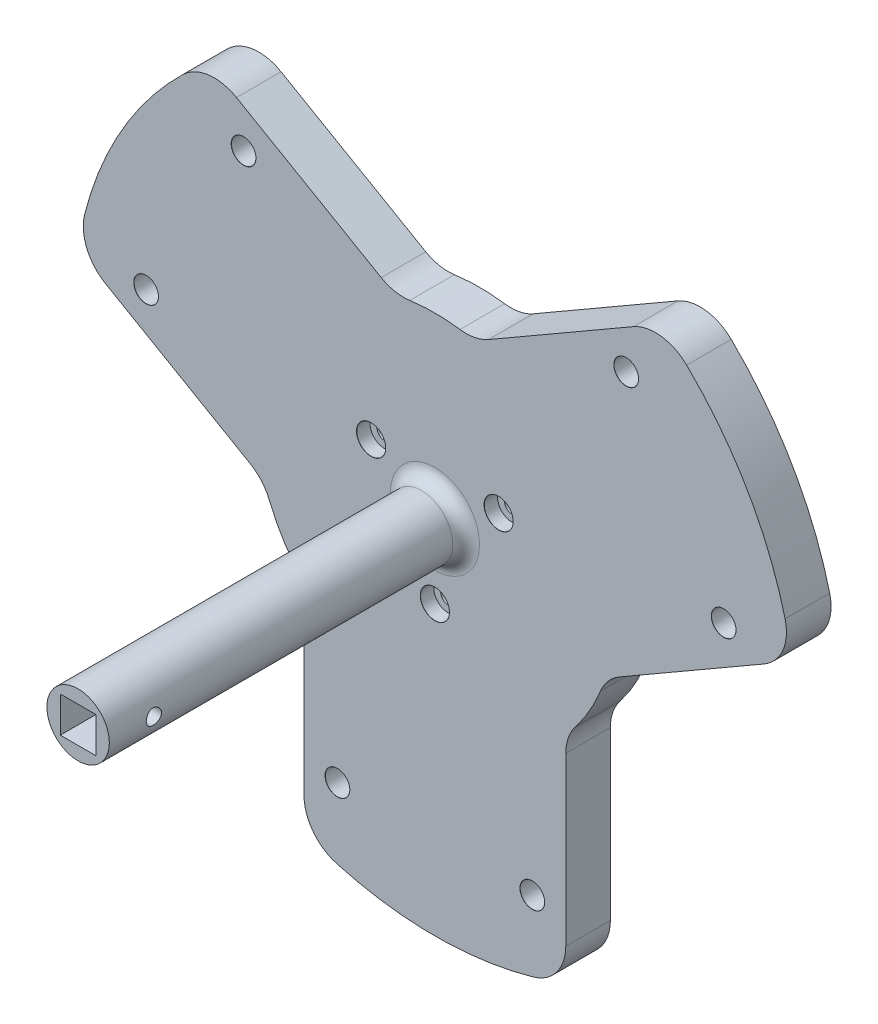
SolidWorks part; units mm, degrees
ref_plane "Front Plane" through (0, 0, 0) normal (0, 0, 1) x (1, 0, 0)
ref_plane "Top Plane" through (0, 0, 0) normal (0, 1, 0) x (1, 0, 0)
ref_plane "Right Plane" through (0, 0, 0) normal (1, 0, 0) x (0, 0, -1)
sketch "Sketch1" plane through (0, 0, 0) normal (0, 0, 1) x (1, 0, 0)
  circle A0 centre (0, 0) radius 81
  dimension "D1" = 162
extrude "Boss-Extrude1" add sketch "Sketch1" along normal blind 10
ref_axis "Axis2" through (0, 0, 38.9853) along (0, 0, -1)
sketch "Sketch2" plane through (0, 0, 10) normal (0, 0, 1) x (1, 0, 0)
  line L0 (0, 0) -> (0, -16.51) construction
  line L1 (-14.2981, 8.255) -> (0, 0) construction
  line L2 (0, 0) -> (14.2981, 8.255) construction
  circle A0 centre (0, 0) radius 16.51 construction
  point P7 (-14.2981, 8.255)
  point P8 (14.2981, 8.255)
  point P9 (0, -16.51)
  dimension "D1" = 16.51
  dimension "D2" = 120
  dimension "D3" = 120
sketch "Sketch5" plane through (0, 0, 10) normal (0, 0, 1) x (1, 0, 0)
  point P0 (-14.2981, 8.255)
  point P3 (14.2981, 8.255)
  point P6 (0, -16.51)
hole_wizard "CBORE for M3 SHCS1" positions "Sketch5" profile "Sketch4" counterbore size "M3" standard "ANSI Metric" end condition up to next
sketch "Sketch4" plane through (-14.2981, 8.255, 10) normal (1, 0, 0) x (0, -1, 0)
  line L0 (0, 0) -> (0, 10)
  line L1 (0, 10) -> (1.7, 10)
  line L3 (1.7, 10) -> (1.7, 3)
  line L4 (3.25, 3) -> (1.7, 3)
  line L5 (3.25, 3) -> (3.25, 0.025)
  line L6 (3.25, 0.025) -> (3.275, 0)
  line L7 (3.275, 0) -> (0, 0)
  line L8 (-3.25, 0.025) -> (-3.275, 0) construction
  line L11 (0, -6.35) -> (0, 107.95) construction
  dimension "Thru Hole Dia." = 3.4
  dimension "Thru Hole Depth" = 10
  dimension "C'Bore Dia." = 6.5
  dimension "C'Bore Depth" = 3
  dimension "Near C'Sink Dia." = 6.55
  dimension "Near C'Sink Angle" = 90
sketch "Sketch6" plane through (0, 0, 10) normal (0, 0, 1) x (1, 0, 0)
  circle A0 centre (0, 0) radius 7
  dimension "D1" = 14
extrude "Boss-Extrude2" add sketch "Sketch6" along normal blind 80
sketch "Sketch20" plane through (0, 0, 90) normal (0, 0, 1) x (1, 0, 0)
  line L1 (-4, 4) -> (4, 4)
  line L2 (-4, 4) -> (-4, -4)
  line L3 (-4, -4) -> (4, -4)
  line L4 (4, 4) -> (4, -4)
  line L5 (-4, 4) -> (4, -4) construction
  line L6 (-4, -4) -> (4, 4) construction
  point P0 (0, 0)
  dimension "D1" = 8
extrude "Cut-Extrude1" cut sketch "Sketch20" against normal blind 20
sketch "Sketch27" plane through (0, 0, 10) normal (0, 0, 1) x (1, 0, 0)
  line L0 (-21.85, -62.15) -> (21.85, -62.15) construction
  line L2 (0, 0) -> (0, -81) construction
  circle A0 centre (0, 0) radius 81 construction
  point P0 (-21.85, -62.15)
  point P2 (21.85, -62.15)
  point P17 (0, -62.15)
  dimension "D1" = 43.7
  dimension "D2" = 62.15
hole_wizard "M5 Clearance Hole3" positions "Sketch27" profile "Sketch26" hole size "M5" standard "ANSI Metric" end condition up to next
sketch "Sketch26" plane through (-21.85, -62.15, 10) normal (1, 0, 0) x (0, -1, 0)
  line L0 (0, 0) -> (0, 10)
  line L1 (0, 10) -> (2.75, 10)
  line L2 (2.75, 10) -> (2.75, 0.025)
  line L3 (2.75, 0.025) -> (2.775, 0)
  line L5 (2.775, 0) -> (0, 0)
  line L6 (-2.75, 0.025) -> (-2.775, 0) construction
  line L11 (0, -6.35) -> (0, 107.95) construction
  dimension "Thru Hole Dia." = 5.5
  dimension "Thru Hole Depth" = 10
  dimension "Near C'Sink Dia." = 5.55
  dimension "Near C'Sink Angle" = 90
pattern_circular "CirPattern1" count 3 over 360 about axis through (0, 0, 38.9853) along (0, 0, -1) of "M5 Clearance Hole3"
ref_plane "Plane1" through (7, 0, 0) normal (1, 0, 0) x (0, 0, -1)
sketch "Sketch34" plane through (7, 0, 0) normal (1, 0, 0) x (0, 0, -1)
  line L0 (-90, 7) -> (-90, -7) construction
  line L1 (-90, 7) -> (-90, -7) construction
  point P0 (-80, 0)
  point P10 (-90, 0)
  dimension "D1" = 10
hole_wizard "M3 Clearance Hole2" positions "Sketch34" profile "Sketch33" hole size "M3" standard "ANSI Metric" end condition through all
sketch "Sketch33" plane through (7, 0, 80) normal (0, 1, 0) x (0, 0, -1)
  line L0 (0, 0) -> (0, 88)
  line L1 (0, 88) -> (1.7, 88)
  line L2 (1.7, 88) -> (1.7, 0.025)
  line L3 (1.7, 0.025) -> (1.725, 0)
  line L5 (1.725, 0) -> (0, 0)
  line L6 (-1.7, 0.025) -> (-1.725, 0) construction
  line L11 (0, -6.35) -> (0, 107.95) construction
  dimension "Thru Hole Dia." = 3.4
  dimension "Thru Hole Depth" = 88
  dimension "Near C'Sink Dia." = 3.45
  dimension "Near C'Sink Angle" = 90
fillet "Fillet1" radius 3 1 edges at (7, 0, 10)
sketch "Sketch35" plane through (0, 0, 10) normal (0, 0, 1) x (1, 0, 0)
  line L0 (-50.7061, 63.1656) -> (-8.8608, 39.0062)
  line L2 (8.8608, 39.0062) -> (50.7061, 63.1656)
  line L3 (0, 0) -> (70.1481, 40.5) construction
  line L4 (29.35, -27.1768) -> (29.35, -75.4955)
  line L5 (80.0561, 12.3299) -> (38.2108, -11.8295)
  line L6 (42.8985, 49.9977) -> (53.8235, 31.075) construction
  line L7 (53.8235, 31.075) -> (64.7485, 12.1523) construction
  line L8 (-38.2108, -11.8295) -> (-80.0561, 12.3299)
  line L9 (-29.35, -75.4955) -> (-29.35, -27.1768)
  circle A0 centre (0, 0) radius 81 construction
  arc A1 (-50.7061, 63.1656) -> (50.7061, 63.1656) centre (0, 0) cw
  circle A3 centre (42.8985, 49.9977) radius 2.775 construction
  arc A4 (-8.8608, 39.0062) -> (8.8608, 39.0062) centre (0, 0) cw
  arc A5 (80.0561, 12.3299) -> (29.35, -75.4955) centre (0, 0) cw
  arc A6 (38.2108, -11.8295) -> (29.35, -27.1768) centre (0, 0) cw
  arc A7 (-29.35, -75.4955) -> (-80.0561, 12.3299) centre (0, 0) cw
  arc A8 (-29.35, -27.1768) -> (-38.2108, -11.8295) centre (0, 0) cw
  point P11 (0, 81)
  point P14 (0, 40)
  point P29 (0, 0)
  dimension "D2" = 7.5
  dimension "D1" = 40
  dimension "D3" = 3
extrude "Cut-Extrude3" cut sketch "Sketch35" against normal blind 10
fillet "Fillet2" radius 10 12 edges at (-50.7061, 63.1656, 5) (-8.8608, 39.0062, 5) (8.8608, 39.0062, 5) (50.7061, 63.1656, 5) (80.0561, 12.3299, 5) (38.2108, -11.8295, 5) (29.35, -27.1768, 5) (29.35, -75.4955, 5) (-29.35, -75.4955, 5) (-29.35, -27.1768, 5) (-38.2108, -11.8295, 5) (-80.0561, 12.3299, 5)
